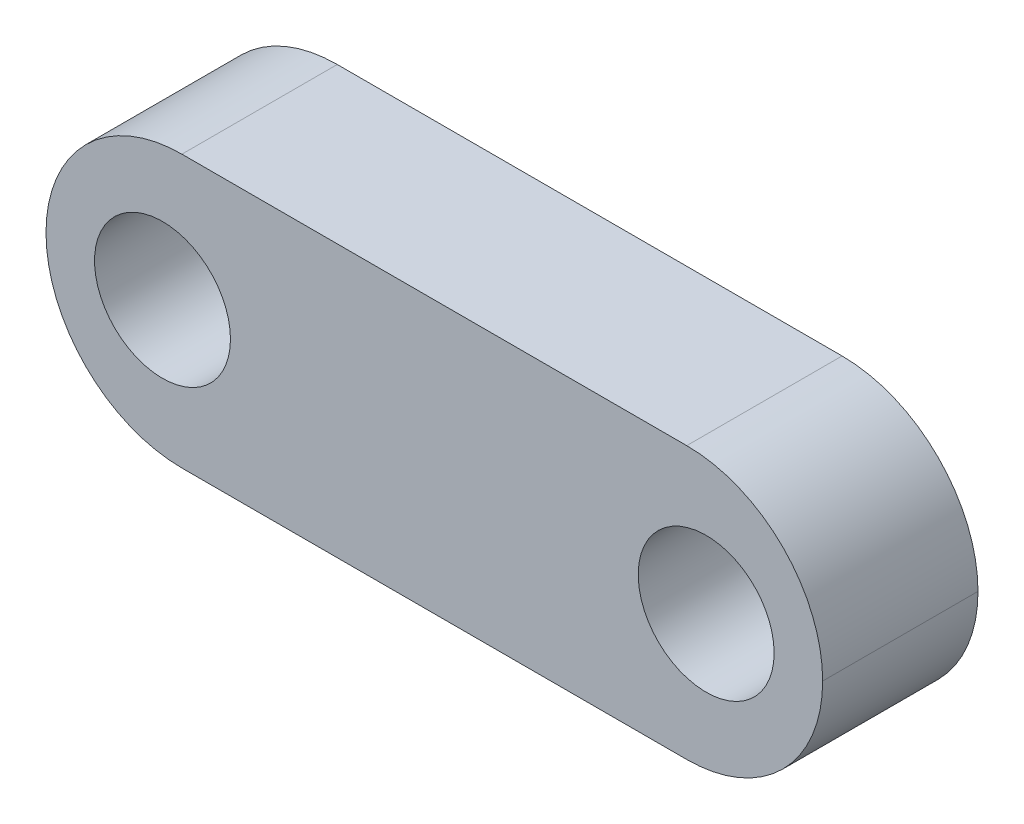
SolidWorks part; units mm, degrees
ref_plane "Front Plane" through (0, 0, 0) normal (0, 0, 1) x (1, 0, 0)
ref_plane "Top Plane" through (0, 0, 0) normal (0, 1, 0) x (1, 0, 0)
ref_plane "Right Plane" through (0, 0, 0) normal (1, 0, 0) x (0, 0, -1)
sketch "Sketch1" plane through (0, 0, 0) normal (0, 0, 1) x (1, 0, 0)
  line L0 (-10, 0) -> (-7, 0)
  line L1 (-10, 3.5) -> (10, 3.5)
  line L2 (-10, 3.5) -> (-10, -3.5)
  line L3 (-10, -3.5) -> (10, -3.5)
  line L4 (10, 3.5) -> (10, -3.5)
  line L5 (-10, 3.5) -> (10, -3.5) construction
  line L6 (-10, -3.5) -> (10, 3.5) construction
  line L7 (10, 0) -> (7, 0)
  circle A0 centre (-7, 0) radius 1.75
  circle A1 centre (7, 0) radius 1.75
  point P0 (0, 0)
  dimension "D4" = 3.5
  dimension "D5" = 3.5
  dimension "D1" = 7
  dimension "D2" = 20
  dimension "D3" = 3
  dimension "D6" = 3
extrude "Boss-Extrude1" add sketch "Sketch1" along normal blind 4 contours L2 L1 L4 L3 | A0 | A1
fillet "Fillet1" radius 3.5 4 edges at (-10, 3.5, 2) (-10, -3.5, 2) (10, -3.5, 2) (10, 3.5, 2)
